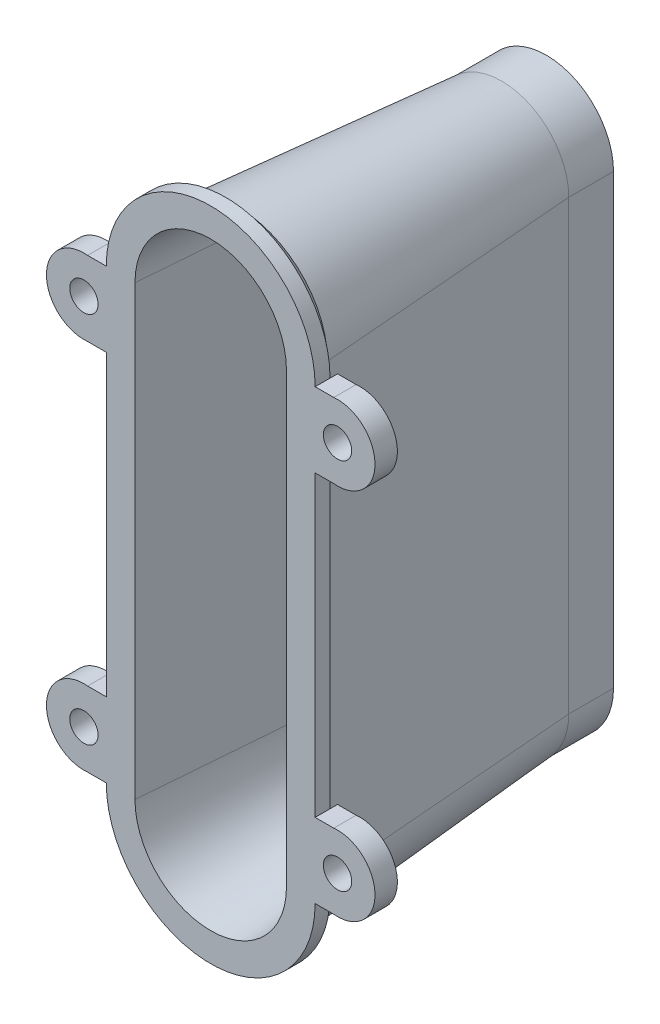
SolidWorks part; units mm, degrees
ref_plane "Płaszczyzna przednia" through (0, 0, 0) normal (0, 0, 1) x (1, 0, 0)
ref_plane "Płaszczyzna górna" through (0, 0, 0) normal (0, 1, 0) x (1, 0, 0)
ref_plane "Płaszczyzna prawa" through (0, 0, 0) normal (1, 0, 0) x (0, 0, -1)
sketch "Szkic1" plane through (0, 0, 0) normal (0, 0, 1) x (1, 0, 0)
  line L0 (0, 0) -> (0, 60) construction
  line L1 (-9, 0) -> (-9, 60)
  line L2 (9, 0) -> (9, 60)
  arc A0 (-9, 0) -> (9, 0) centre (0, 0) ccw
  arc A1 (9, 60) -> (-9, 60) centre (0, 60) ccw
  point P3 (0, 30)
  dimension "D2" = 9
  dimension "D1" = 60
extrude "Dodanie-wyciągnięcie1" add sketch "Szkic1" along normal blind 45
sketch "Szkic2" plane through (0, 0, 45) normal (0, 0, 1) x (1, 0, 0)
  line L0 (0, 60) -> (0, 0) construction
  line L1 (14, 60) -> (14, 0)
  line L2 (-14, 60) -> (-14, 0)
  arc A0 (14, 60) -> (-14, 60) centre (0, 60) ccw
  arc A1 (-14, 0) -> (14, 0) centre (0, 0) ccw
  point P4 (0, 30)
  dimension "D1" = 14
extrude "Dodanie-wyciągnięcie2" add sketch "Szkic2" against normal blind 2
chamfer "Sfazowanie1" distance 37 distance2 3 4 edges at (-9, 30, 43) (0, -9, 43) (0, 69, 43) (9, 30, 43) first distance on face at (-9, 30, 21.5) first distance on face at (0, -4.5, 21.5) first distance on face at (0, 64.5, 21.5) first distance on face at (9, 30, 21.5)
shell "Skorupa4" thickness 2 removed face at (0, 30, 0) removed face at (0, 30, 45)
sketch "Szkic5" plane through (0, 0, 43) normal (0, 0, -1) x (-1, 0, 0)
  line L0 (-14, 0) -> (-14, 60) construction
  line L1 (-12, 0) -> (-14, 0)
  line L2 (-12, 0) -> (-12, 10)
  line L3 (-12, 10) -> (-14, 10)
  line L4 (-14, 0) -> (-14, 10)
  line L5 (-8.5135, 30) -> (6.507, 30) construction
  line L6 (-8.5135, 0) -> (-8.5135, 60) construction
  line L7 (6.507, 60) -> (6.507, 0) construction
  line L8 (0, -6.507) -> (0, 30) construction
  line L9 (14, 0) -> (14, 10)
  line L10 (12, 10) -> (14, 10)
  line L11 (12, 0) -> (12, 10)
  line L12 (12, 0) -> (14, 0)
  line L13 (12, 60) -> (14, 60)
  line L14 (12, 60) -> (12, 50)
  line L15 (12, 50) -> (14, 50)
  line L16 (14, 60) -> (14, 50)
  line L17 (-14, 60) -> (-14, 50)
  line L18 (-12, 50) -> (-14, 50)
  line L19 (-12, 60) -> (-12, 50)
  line L20 (-12, 60) -> (-14, 60)
  arc A0 (6.507, 0) -> (-6.507, 0) centre (0, 0) ccw construction
  dimension "D1" = 10
sketch "Szkic11" plane through (0, 0, 45) normal (0, 0, 1) x (1, 0, 0)
  line L0 (10.1556, 30) -> (-6.507, 30) construction
  line L1 (14, 0) -> (16.5, 0)
  line L2 (14, 0) -> (14, 10)
  line L3 (14, 10) -> (16.5, 10)
  line L4 (10.1556, 0) -> (10.1556, 60) construction
  line L5 (-6.507, 60) -> (-6.507, 0) construction
  line L6 (0, 66.507) -> (0, 30) construction
  line L7 (-14, 10) -> (-16.5, 10)
  line L8 (-14, 0) -> (-14, 10)
  line L9 (-14, 0) -> (-16.5, 0)
  line L10 (-14, 60) -> (-16.5, 60)
  line L11 (-14, 60) -> (-14, 50)
  line L12 (-14, 50) -> (-16.5, 50)
  line L13 (14, 50) -> (16.5, 50)
  line L14 (14, 60) -> (14, 50)
  line L15 (14, 60) -> (16.5, 60)
  arc A0 (16.5, 0) -> (16.5, 10) centre (17, 5) ccw
  circle A1 centre (17, 5) radius 1.9
  arc A2 (-6.507, 60) -> (6.507, 60) centre (0, 60) ccw construction
  circle A3 centre (-17, 5) radius 1.9
  arc A4 (-16.5, 0) -> (-16.5, 10) centre (-17, 5) cw
  arc A5 (-16.5, 60) -> (-16.5, 50) centre (-17, 55) ccw
  circle A6 centre (-17, 55) radius 1.9
  circle A7 centre (17, 55) radius 1.9
  arc A8 (16.5, 60) -> (16.5, 50) centre (17, 55) cw
  dimension "D3" = 3
  dimension "D4" = 3.8
  dimension "D1" = 10
  dimension "D2" = 2.5
extrude "Dodanie-wyciągnięcie11" add sketch "Szkic11" against normal blind 3
chamfer "Sfazowanie6" distance 1.8 angle 45 4 edges at (-12, 30, 43) (0, -12, 43) (0, 72, 43) (12, 30, 43) first distance on face at (-10.5, 30, 24.5) first distance on face at (0, -5.25, 24.5) first distance on face at (0, 65.25, 24.5) first distance on face at (10.5, 30, 24.5)
